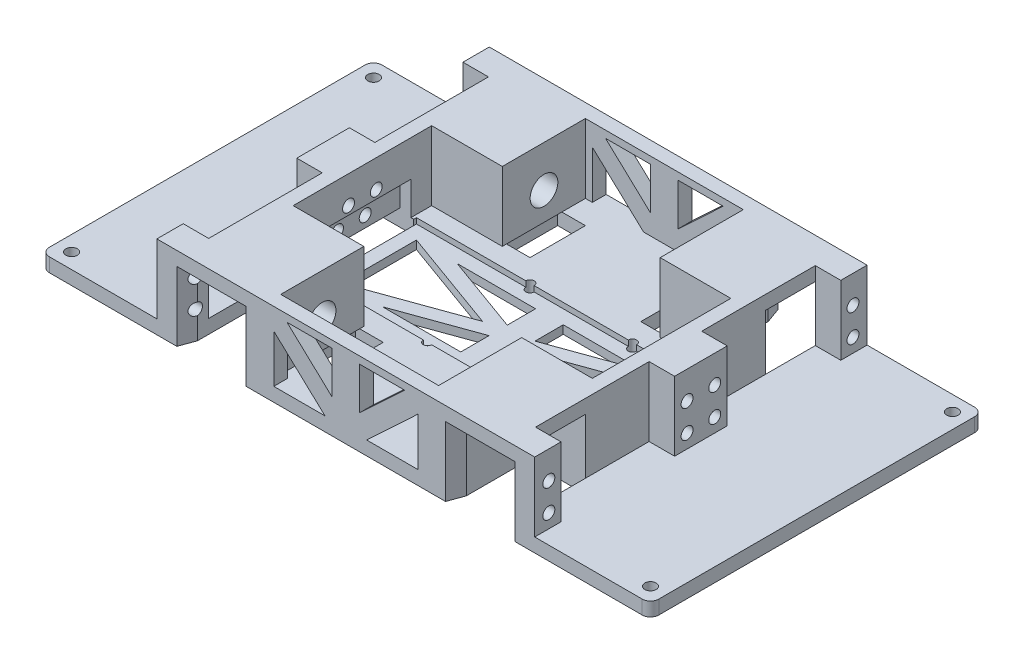
SolidWorks part; units mm, degrees
ref_plane "前基準面" through (0, 0, 0) normal (0, 0, 1) x (1, 0, 0)
ref_plane "上基準面" through (0, 0, 0) normal (0, 1, 0) x (1, 0, 0)
ref_plane "右基準面" through (0, 0, 0) normal (1, 0, 0) x (0, 0, -1)
sketch "草圖1" plane through (0, 0, 0) normal (0, 1, 0) x (1, 0, 0)
  line L0 (0, 0) -> (0, 78.9859) construction
  line L1 (-110, -60) -> (-59, -60)
  line L2 (-110, -60) -> (-110, 60)
  line L3 (-110, 60) -> (-59, 60)
  line L4 (110, -60) -> (110, 60)
  line L5 (-110, -60) -> (110, 60) construction
  line L6 (-110, 60) -> (110, -60) construction
  line L7 (-38, 60) -> (38, 60)
  line L9 (-59, 60) -> (-59, 32.5)
  line L10 (-59, 32.5) -> (-38, 32.5)
  line L11 (-38, 60) -> (-38, 32.5)
  line L12 (38, 60) -> (38, 32.5)
  line L13 (59, 32.5) -> (38, 32.5)
  line L14 (59, 60) -> (59, 32.5)
  line L15 (0, 0) -> (138.7363, 0) construction
  line L16 (59, -32.5) -> (38, -32.5)
  line L17 (59, -60) -> (59, -32.5)
  line L18 (38, -60) -> (38, -32.5)
  line L19 (-38, -60) -> (-38, -32.5)
  line L20 (-59, -32.5) -> (-38, -32.5)
  line L21 (-59, -60) -> (-59, -32.5)
  line L22 (59, 60) -> (110, 60)
  line L23 (59, -60) -> (110, -60)
  line L24 (-38, -60) -> (38, -60)
  point P0 (0, 0)
  dimension "D1" = 220
  dimension "D2" = 120
  dimension "D3" = 51
  dimension "D4" = 21
  dimension "D5" = 27.5
extrude "填料-伸長1" add sketch "草圖1" along normal blind 5
sketch "草圖9" plane through (0, 5, 0) normal (0, 1, 0) x (1, 0, 0)
  line L1 (-53, -18.5) -> (53, -18.5)
  line L2 (-53, -18.5) -> (-53, 18.5)
  line L3 (-53, 18.5) -> (53, 18.5)
  line L4 (53, -18.5) -> (53, 18.5)
  line L5 (-53, -18.5) -> (53, 18.5) construction
  line L6 (-53, 18.5) -> (53, -18.5) construction
  dimension "D1" = 106
  dimension "D2" = 37
extrude "除料-伸長5" cut sketch "草圖9" against normal blind 2
sketch "草圖2" plane through (0, 5, 0) normal (0, 1, 0) x (1, 0, 0)
  line L0 (0, 0) -> (213.5831, 0) construction
  line L28 (0, 0) -> (0, 101.5292) construction
  line L42 (-59, 32.5) -> (-59, 9.5)
  line L46 (59, 32.5) -> (59, 9.5)
  line L56 (-28.5, 55) -> (28.5, 55)
  line L59 (-28.5, 55) -> (-28.5, 25)
  line L92 (28.5, 55) -> (28.5, 25)
  line L99 (28.5, -55) -> (28.5, -25)
  line L141 (-28.5, -55) -> (28.5, -55)
  line L142 (-28.5, -55) -> (-28.5, -25)
  line L143 (-59, 32.5) -> (-59, 60) construction
  line L144 (-59, -32.5) -> (-38, -32.5) construction
  line L145 (28.5, -25) -> (54, -25)
  line L146 (-28.5, 25) -> (-54, 25)
  line L148 (-28.5, -25) -> (-54, -25)
  line L149 (-54, 25) -> (-54, -25)
  line L150 (28.5, 25) -> (54, 25)
  line L151 (54, 25) -> (54, -25)
  line L152 (68.2, 9.5) -> (59, 9.5)
  line L153 (110, 60) -> (59, 60)
  line L154 (59, 60) -> (59, 32.5)
  line L155 (59, 32.5) -> (38, 32.5)
  line L156 (38, 32.5) -> (38, 60)
  line L157 (38, 60) -> (-38, 60)
  line L158 (-38, 60) -> (-38, 32.5)
  line L159 (-38, 32.5) -> (-59, 32.5)
  line L160 (-59, 32.5) -> (-59, 60)
  line L161 (-59, 60) -> (-110, 60)
  line L162 (-110, 60) -> (-110, -60)
  line L163 (-110, -60) -> (-59, -60)
  line L164 (-59, -60) -> (-59, -32.5)
  line L165 (-59, -32.5) -> (-38, -32.5)
  line L166 (-38, -32.5) -> (-38, -60)
  line L167 (-38, -60) -> (38, -60)
  line L168 (38, -60) -> (38, -32.5)
  line L169 (38, -32.5) -> (59, -32.5)
  line L170 (59, -32.5) -> (59, -60)
  line L171 (59, -60) -> (110, -60)
  line L172 (110, -60) -> (110, 60)
  line L175 (59, 32.5) -> (38, 32.5)
  line L176 (38, 32.5) -> (38, 60)
  line L177 (38, 60) -> (-38, 60)
  line L178 (-38, 60) -> (-38, 32.5)
  line L179 (-38, 32.5) -> (-59, 32.5)
  line L185 (-59, -32.5) -> (-38, -32.5)
  line L186 (-38, -32.5) -> (-38, -60)
  line L187 (-38, -60) -> (38, -60)
  line L188 (38, -60) -> (38, -32.5)
  line L189 (38, -32.5) -> (59, -32.5)
  line L193 (-68.2, -9.5) -> (-59, -9.5)
  line L194 (-68.2, -9.5) -> (-68.2, 9.5)
  line L195 (-68.2, 9.5) -> (-59, 9.5)
  line L198 (68.2, -9.5) -> (59, -9.5)
  line L199 (68.2, -9.5) -> (68.2, 9.5)
  line L200 (-59, -9.5) -> (-59, -32.5)
  line L201 (59, -9.5) -> (59, -32.5)
  line L202 (-59, 60) -> (-110, 60) construction
  line L203 (-59, 60) -> (-68.2, 60)
  line L204 (-59, 60) -> (-59, 50.5)
  line L205 (-59, 50.5) -> (-68.2, 50.5)
  line L206 (-68.2, 60) -> (-68.2, 50.5)
  line L207 (59, 50.5) -> (68.2, 50.5)
  line L208 (68.2, 60) -> (68.2, 50.5)
  line L209 (59, 60) -> (68.2, 60)
  line L210 (59, 60) -> (59, 50.5)
  line L211 (59, -60) -> (59, -50.5)
  line L212 (59, -60) -> (68.2, -60)
  line L213 (68.2, -60) -> (68.2, -50.5)
  line L214 (59, -50.5) -> (68.2, -50.5)
  line L215 (-59, -50.5) -> (-68.2, -50.5)
  line L216 (-68.2, -60) -> (-68.2, -50.5)
  line L217 (-59, -60) -> (-68.2, -60)
  line L218 (-59, -60) -> (-59, -50.5)
  dimension "D3" = 9.5
  dimension "D4" = 5
  dimension "D5" = 50
  dimension "D2" = 5
  dimension "D6" = 9.2
  dimension "D7" = 19
  dimension "D8" = 9.5
  dimension "D1" = 0
extrude "填料-伸長2" add sketch "草圖2" along normal blind 25
sketch "草圖4" plane through (0, 0, 0) normal (1, 0, 0) x (0, 0, -1)
  line L0 (0, 0) -> (0, 52.9301) construction
  circle A0 centre (-5, 20) radius 2.15
  circle A1 centre (-5, 10) radius 2.15
  circle A2 centre (5, 10) radius 2.15
  circle A3 centre (5, 20) radius 2.15
  dimension "D1" = 4.3
  dimension "D2" = 10
  dimension "D3" = 10
  dimension "D4" = 10
extrude "除料-伸長1" cut sketch "草圖4" against normal through all both and the other way through all
sketch "草圖6" plane through (0, 0, 0) normal (1, 0, 0) x (0, 0, -1)
  line L0 (0, 0) -> (0, 66.2046) construction
  line L1 (60, 0) -> (-60, 0) construction
  circle A0 centre (-40.05, 15.0067) radius 5
  circle A1 centre (40.05, 15.0067) radius 5
  dimension "D1" = 10
extrude "除料-伸長2" cut sketch "草圖6" against normal mid plane 90
sketch "草圖7" plane through (-68.2, 0, 0) normal (-1, 0, 0) x (0, 0, 1)
  line L0 (0, 0) -> (0, 45.7304) construction
  line L1 (-60, 0) -> (60, 0) construction
  circle A0 centre (-54.9, 20) radius 2.15
  circle A1 centre (-54.9, 10.0067) radius 2.15
  circle A2 centre (54.9, 10.0067) radius 2.15
  circle A3 centre (54.9, 20) radius 2.15
  dimension "D2" = 4.3
  dimension "D1" = 54.9
extrude "除料-伸長3" cut sketch "草圖7" against normal up to next
sketch "草圖8" plane through (68.2, 0, 0) normal (1, 0, 0) x (0, 0, -1)
  circle A4 centre (-54.9, 10.0067) radius 2.15
  circle A5 centre (-54.9, 20) radius 2.15
  circle A6 centre (54.9, 10.0067) radius 2.15
  circle A7 centre (54.9, 20) radius 2.15
  point P13 (0, 0)
  dimension "D2" = 4.3
  dimension "D1" = 54.9
extrude "除料-伸長4" cut sketch "草圖8" against normal up to next
sketch "草圖10" plane through (0, 5, 0) normal (0, 1, 0) x (1, 0, 0)
  line L0 (0, 0) -> (0, 80.1377) construction
  line L2 (-58, 17.5) -> (-53, 17.5)
  line L3 (-58, 17.5) -> (-58, -17.5)
  line L4 (-58, -17.5) -> (-53, -17.5)
  line L5 (-53, 17.5) -> (-53, -17.5)
  line L6 (0, 0) -> (26.0198, 0) construction
  line L7 (58, -17.5) -> (53, -17.5)
  line L8 (53, 17.5) -> (53, -17.5)
  line L9 (58, 17.5) -> (58, -17.5)
  line L10 (58, 17.5) -> (53, 17.5)
  point P6 (-85.7328, 10.0975)
  point P14 (0, 0)
  point P17 (0, 0)
  point P20 (0, 0)
  dimension "D1" = 5
  dimension "D2" = 35
  dimension "D3" = 53
extrude "除料-伸長6" cut sketch "草圖10" against normal through all and the other way blind 12
sketch "草圖11" plane through (0, 5, 0) normal (0, 1, 0) x (1, 0, 0)
  line L0 (0, 0) -> (0, 44.5869) construction
  line L1 (0, 0) -> (22.9255, 0) construction
  line L2 (-48, 13.5) -> (-48, -13.5)
  line L3 (-48, -13.5) -> (-10.6314, 0)
  line L4 (-10.6314, 0) -> (-48, 13.5)
  line L5 (-33.2843, 13.5) -> (-5, 13.5)
  line L6 (-5, 13.5) -> (-5, 3.2818)
  line L7 (-5, 3.2818) -> (-33.2843, 13.5)
  line L8 (48, -13.5) -> (10.6314, 0)
  line L9 (48, 13.5) -> (48, -13.5)
  line L10 (10.6314, 0) -> (48, 13.5)
  line L11 (5, 13.5) -> (5, 3.2818)
  line L12 (33.2843, 13.5) -> (5, 13.5)
  line L13 (5, 3.2818) -> (33.2843, 13.5)
  line L14 (33.2843, -13.5) -> (5, -13.5)
  line L15 (5, -3.2818) -> (33.2843, -13.5)
  line L16 (5, -13.5) -> (5, -3.2818)
  line L17 (-5, -13.5) -> (-5, -3.2818)
  line L18 (-33.2843, -13.5) -> (-5, -13.5)
  line L19 (-5, -3.2818) -> (-33.2843, -13.5)
  line L20 (30, 26.5) -> (20, 26.5)
  line L21 (-53, 18.5) -> (-53, 17.5) construction
  line L22 (53, 18.5) -> (-53, 18.5) construction
  line L23 (110, 60) -> (68.2, 60) construction
  line L24 (110, -60) -> (110, 60) construction
  line L25 (-30, 46.5) -> (-20, 46.5)
  line L26 (-30, 46.5) -> (-30, 26.5)
  line L27 (-30, 26.5) -> (-20, 26.5)
  line L28 (-20, 46.5) -> (-20, 26.5)
  line L29 (20, 46.5) -> (20, 26.5)
  line L30 (30, 46.5) -> (20, 46.5)
  line L31 (30, 46.5) -> (30, 26.5)
  line L32 (30, -46.5) -> (30, -26.5)
  line L33 (30, -46.5) -> (20, -46.5)
  line L34 (20, -46.5) -> (20, -26.5)
  line L35 (30, -26.5) -> (20, -26.5)
  line L36 (-30, -26.5) -> (-20, -26.5)
  line L37 (-20, -46.5) -> (-20, -26.5)
  line L38 (-30, -46.5) -> (-20, -46.5)
  line L39 (-30, -46.5) -> (-30, -26.5)
  circle A0 centre (104.5, 54.5) radius 2.05
  circle A1 centre (-104.5, 54.5) radius 2.05
  circle A2 centre (-104.5, -54.5) radius 2.05
  circle A3 centre (104.5, -54.5) radius 2.05
  circle A4 centre (-12, 18.5) radius 1.5
  circle A5 centre (25, 18.5) radius 1.5
  circle A6 centre (25, -18.5) radius 1.5
  circle A7 centre (-12, -18.5) radius 1.5
  dimension "D3" = 4.1
  dimension "D10" = 3
  dimension "D2" = 5.5
  dimension "D4" = 5
  dimension "D5" = 5
  dimension "D6" = 5
  dimension "D7" = 10
  dimension "D8" = 12
  dimension "D9" = 25
  dimension "D11" = 5.5
  dimension "D12" = 40
  dimension "D13" = 10
  dimension "D14" = 20
  dimension "D15" = 8
extrude "除料-伸長7" cut sketch "草圖11" against normal through all
sketch "草圖12" plane through (0, 30, 0) normal (0, 1, 0) x (1, 0, 0)
  line L0 (0, 0) -> (0, 65.905) construction
  line L1 (0, 0) -> (64.3084, 0) construction
  line L2 (-68.2, 60) -> (-110, 60) construction
  line L3 (-59, 60) -> (-28.5, 60)
  line L4 (-59, 60) -> (-59, 25)
  line L5 (-59, 25) -> (-28.5, 25)
  line L6 (-28.5, 60) -> (-28.5, 25)
  line L7 (-59, 60) -> (-68.2, 60) construction
  line L8 (-28.5, 55) -> (-28.5, 25) construction
  line L9 (59, 25) -> (28.5, 25)
  line L10 (28.5, 60) -> (28.5, 25)
  line L11 (59, 60) -> (28.5, 60)
  line L12 (59, 60) -> (59, 25)
  line L13 (59, -60) -> (59, -25)
  line L14 (59, -60) -> (28.5, -60)
  line L15 (28.5, -60) -> (28.5, -25)
  line L16 (59, -25) -> (28.5, -25)
  line L17 (-59, -25) -> (-28.5, -25)
  line L18 (-28.5, -60) -> (-28.5, -25)
  line L19 (-59, -60) -> (-28.5, -60)
  line L20 (-59, -60) -> (-59, -25)
  line L23 (-59, 50.5) -> (-59, 60) construction
  point P25 (-30, 25)
  point P27 (-60.5, 60)
extrude "填料-伸長3" add sketch "草圖12" against normal blind 5
sketch "草圖13" plane through (0, 0, 0) normal (0, 0, 1) x (1, 0, 0)
  line L0 (0, 0) -> (0, 45.7733) construction
  line L1 (-26, 22.2891) -> (-26, 5)
  line L2 (-26, 5) -> (-7.5, 5)
  line L3 (-7.5, 5) -> (-26, 22.2891)
  line L4 (-21.2448, 27.4262) -> (-5, 12.2446)
  line L5 (-5, 12.2446) -> (-5, 27.4262)
  line L6 (-5, 27.4262) -> (-21.2448, 27.4262)
  line L7 (26, 5) -> (7.5, 5)
  line L8 (26, 22.2891) -> (26, 5)
  line L9 (7.5, 5) -> (26, 22.2891)
  line L10 (5, 12.2446) -> (5, 27.4262)
  line L11 (21.2448, 27.4262) -> (5, 12.2446)
  line L12 (5, 27.4262) -> (21.2448, 27.4262)
  line L13 (-38, 25) -> (-38, 0) construction
  line L14 (-38, 0) -> (38, 0) construction
  dimension "D1" = 12
  dimension "D3" = 10
  dimension "D4" = 15
  dimension "D6" = 7
extrude "除料-伸長8" cut sketch "草圖13" against normal through all both and the other way through all
chamfer "導角1" distance 1.5 angle 50 4 edges at (38, 15.0067, -35.05) (-38, 15.0067, -45.05) (38, 15.0067, 45.05) (-38, 15.0067, 35.05)
fillet "圓角1" radius 3 4 edges at (-110, 2.5, 60) (110, 2.5, 60) (110, 2.5, -60) (-110, 2.5, -60)
chamfer "導角2" distance 6 angle 45 2 edges at (58, 0, 0) (-58, 0, 0)
chamfer "導角3" distance 2 angle 70 8 edges at (-38, 12.5, -60) (-59, 12.5, -60) (38, 12.5, -60) (59, 12.5, -60) (59, 12.5, 60) (38, 12.5, 60) (-38, 12.5, 60) (-59, 12.5, 60)
